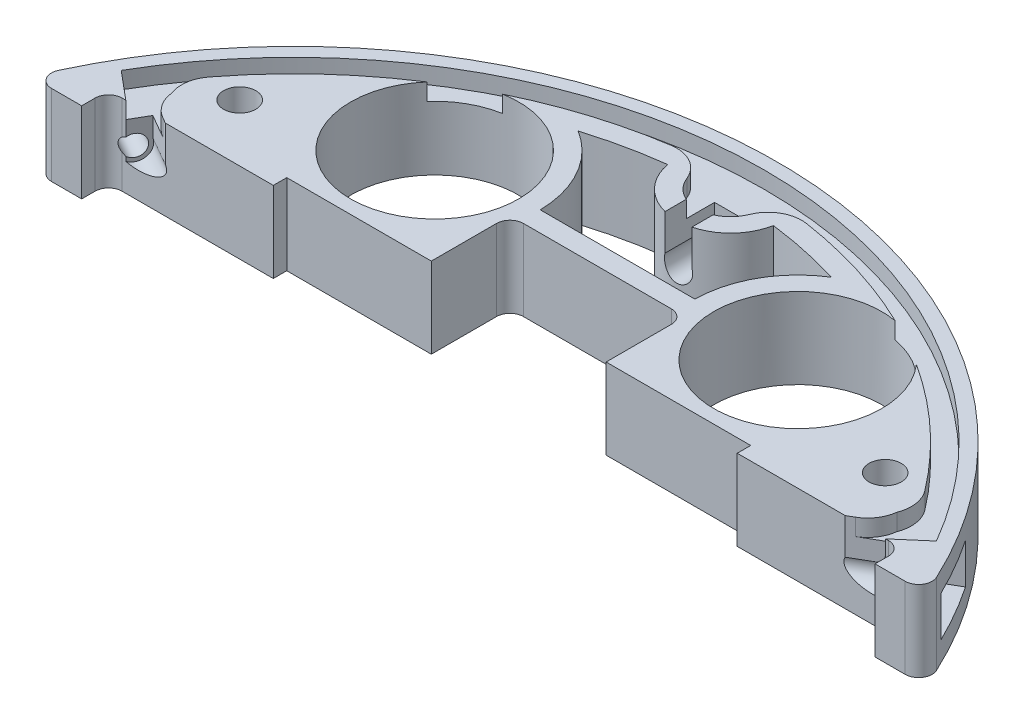
SolidWorks part; units mm, degrees
material "ABS"
ref_plane "Front Plane" through (0, 0, 0) normal (0, 0, 1) x (1, 0, 0)
ref_plane "Top Plane" through (0, 0, 0) normal (0, 1, 0) x (1, 0, 0)
ref_plane "Right Plane" through (0, 0, 0) normal (1, 0, 0) x (0, 0, -1)
sketch "Sketch1" plane through (0, 0, 0) normal (0, 1, 0) x (1, 0, 0)
  line L0 (0, -85) -> (-32.2211, -64.3879) construction
  line L1 (0, -85) -> (0, 0) construction
  arc A0 (36.2245, -62.2237) -> (-36.2245, -62.2237) centre (0, 0) ccw
  arc A1 (29.8119, -61.0352) -> (-29.8119, -61.0352) centre (0, -85) ccw
  arc A2 (36.2245, -62.2237) -> (29.8119, -61.0352) centre (33.7089, -57.9026) cw
  arc A3 (-29.8119, -61.0352) -> (-36.2245, -62.2237) centre (-33.7089, -57.9026) cw
  dimension "D1" = 144
  dimension "D2" = 76.5
  dimension "D4" = 5
  dimension "D3" = 85
extrude "Boss-Extrude1" add sketch "Sketch1" along normal mid plane 12
sketch "solenoid placement" plane through (0, 6, 0) normal (0, 1, 0) x (1, 0, 0)
  line L0 (0, 0) -> (0, -36) construction
  line L5 (-19, -36) -> (19, -36)
  line L7 (19, -36) -> (19, 28)
  line L9 (19, 28) -> (-19, 28)
  line L11 (-19, 28) -> (-19, -36)
  circle A1 centre (0, 0) radius 72 construction
  arc A2 (36.2245, -62.2237) -> (-36.2245, -62.2237) centre (0, 0) ccw construction
  dimension "D1" = 36
  dimension "D2" = 64
  dimension "D3" = 38
extrude "Cut-Extrude1" cut sketch "solenoid placement" against normal through all
sketch "Sketch4" plane through (0, 6, 0) normal (0, 1, 0) x (1, 0, 0)
  line L1 (-13, 28) -> (13, 28)
  line L2 (-13, 28) -> (-13, 43.2)
  line L4 (13, 28) -> (13, 43.2)
  line L5 (11, 45.2) -> (-11, 45.2)
  line L6 (19, 28) -> (-19, 28) construction
  arc A0 (11, 45.2) -> (13, 43.2) centre (11, 43.2) cw
  arc A1 (-11, 45.2) -> (-13, 43.2) centre (-11, 43.2) ccw
  point P6 (0, 28)
  dimension "D1" = 2
  dimension "D2" = 26
  dimension "D3" = 17.2
extrude "Cut-Extrude4" cut sketch "Sketch4" against normal through all
sketch "Sketch5" plane through (0, 6, 0) normal (0, 1, 0) x (1, 0, 0)
  line L0 (0, 0) -> (0, 72) construction
  arc A0 (36.2245, -62.2237) -> (-36.2245, -62.2237) centre (0, 0) ccw construction
  circle A1 centre (27, 48) radius 12.5
  circle A3 centre (-27, 48) radius 12.5
  dimension "D3" = 25
  dimension "D1" = 27
  dimension "D2" = 48
extrude "Cut-Extrude5" cut sketch "Sketch5" against normal through all
sketch "Sketch6" plane through (0, 6, 0) normal (0, 1, 0) x (1, 0, 0)
  line L0 (0, 0) -> (0, 72) construction
  arc A0 (36.2245, -62.2237) -> (-36.2245, -62.2237) centre (0, 0) ccw construction
  circle A1 centre (48, 40) radius 2.4
  circle A6 centre (-48, 40) radius 2.4
  dimension "D3" = 4.8
  dimension "D1" = 48
  dimension "D2" = 40
extrude "Cut-Extrude6" cut sketch "Sketch6" against normal through all
sketch "Sketch3" plane through (0, 6, 0) normal (0, 1, 0) x (1, 0, 0)
  line L1 (-72, -31.5) -> (72, -31.5) construction
  line L2 (-72, -31.5) -> (-72, 27.5)
  line L3 (-59, 31.5) -> (0, 31.5)
  line L4 (72, -31.5) -> (72, 27.5)
  line L5 (0, -31.5) -> (0, 31.5) construction
  line L6 (72, 27.5) -> (59, 27.5)
  line L9 (0, 31.5) -> (59, 31.5)
  line L10 (-72, -31.5) -> (-72, -101.6464)
  line L11 (72, -31.5) -> (72, -101.6464)
  line L12 (72, -101.6464) -> (-72, -101.6464)
  line L13 (59, 27.5) -> (59, 31.5)
  line L14 (-59, 27.5) -> (-59, 31.5)
  line L15 (-72, 27.5) -> (-59, 27.5)
  arc A0 (36.2245, -62.2237) -> (-36.2245, -62.2237) centre (0, 0) ccw construction
  point P0 (0, 0)
  dimension "D2" = 13
  dimension "D1" = 63
  dimension "D3" = 4
extrude "Cut-Extrude3" cut sketch "Sketch3" against normal through all
sketch "Sketch7" plane through (0, 0, 0) normal (0, 1, 0) x (1, 0, 0)
  line L0 (0, 0) -> (62.3538, 36) construction
  line L1 (0, 0) -> (-62.3538, 36) construction
  line L2 (0, 0) -> (0, 72) construction
  arc A0 (0, 72) -> (62.3538, 36) centre (0, 0) cw construction
  arc A1 (0, 72) -> (-62.3538, 36) centre (0, 0) ccw construction
  arc A2 (66.5413, 27.5) -> (-66.5413, 27.5) centre (0, 0) ccw construction
  dimension "D1" = 120
fillet "Fillet1" radius 2 4 edges at (-66.5413, 0, -27.5) (-59, 0, -31.5) (59, 0, -31.5) (66.5413, 0, -27.5)
sketch "Sketch8" plane through (0, 0, 0) normal (0, 1, 0) x (1, 0, 0)
  line L0 (5, 71.8262) -> (5, 68.8262)
  line L1 (0, 0) -> (64.7033, 31.583) construction
  line L2 (64.7033, 31.583) -> (59.7033, 40.2432) construction
  line L3 (64.7033, 31.583) -> (62.1052, 30.083)
  line L4 (62.1052, 30.083) -> (57.1052, 38.7432)
  line L5 (59.7033, 40.2432) -> (57.1052, 38.7432)
  line L6 (0, 0) -> (59.7033, 40.2432) construction
  line L7 (5, 68.8262) -> (-5, 68.8262)
  line L8 (-5, 71.8262) -> (-5, 68.8262)
  line L9 (5, 71.8262) -> (-5, 71.8262) construction
  line L10 (-59.7033, 40.2432) -> (-57.1052, 38.7432)
  line L11 (-57.1052, 38.7432) -> (-62.1052, 30.083)
  line L12 (-64.7033, 31.583) -> (-62.1052, 30.083)
  line L13 (-59.7033, 40.2432) -> (-64.7033, 31.583) construction
  arc A0 (59.7033, 40.2432) -> (64.7033, 31.583) centre (0, 0) cw
  arc A2 (-5, 71.8262) -> (5, 71.8262) centre (0, 0) cw
  arc A3 (-64.7033, 31.583) -> (-59.7033, 40.2432) centre (0, 0) cw
  point P4 (62.3538, 36)
  point P10 (-62.3538, 36)
  point P18 (0, 0)
  dimension "D1" = 10
  dimension "D2" = 3
extrude "Cut-Extrude7" cut sketch "Sketch8" against normal mid plane 6
sketch "Sketch10" plane through (0, 6, 0) normal (0, 1, 0) x (1, 0, 0)
  line L0 (0, 0) -> (0, 65) construction
  circle A0 centre (0, 65) radius 5
  dimension "D2" = 10
  dimension "D1" = 65
extrude "Cut-Extrude9" cut sketch "Sketch10" against normal blind 2.5
sketch "Sketch11" plane through (0, 6, 0) normal (0, 1, 0) x (1, 0, 0)
  line L1 (34.5, -33.5) -> (-34.5, -33.5)
  line L2 (34.5, -33.5) -> (34.5, 33.5)
  line L3 (34.5, 33.5) -> (-34.5, 33.5)
  line L4 (-34.5, -33.5) -> (-34.5, 33.5)
  line L5 (34.5, -33.5) -> (-34.5, 33.5) construction
  line L6 (34.5, 33.5) -> (-34.5, -33.5) construction
  point P0 (0, 0)
  dimension "D1" = 67
  dimension "D2" = 69
extrude "Cut-Extrude10" cut sketch "Sketch11" against normal through all
sketch "Sketch13" plane through (-59.6052, 0, -34.4131) normal (-0.866, 0, -0.5) x (-0.5, 0, 0.866)
  circle A0 centre (0, 0) radius 1.55
  dimension "D1" = 3.1
extrude "Cut-Extrude11" cut sketch "Sketch13" against normal blind 4.2
sketch "Sketch14" plane through (-55.9679, 0, -32.3131) normal (-0.866, 0, -0.5) x (-0.5, 0, 0.866)
  circle A0 centre (0, 0) radius 2.1
  dimension "D1" = 4.2
extrude "Cut-Extrude12" cut sketch "Sketch14" against normal blind 9
sketch "Sketch15" plane through (-55.9679, 0, -32.3131) normal (0.866, 0, 0.5) x (0.5, 0, -0.866)
  line L1 (-2, 0) -> (2, 0)
  line L2 (-2, 0) -> (-2, 10.8827)
  line L3 (-2, 10.8827) -> (2, 10.8827)
  line L4 (2, 0) -> (2, 10.8827)
  point P0 (0, 0)
  dimension "D1" = 4
extrude "Cut-Extrude13" cut sketch "Sketch15" along normal blind 9
pattern_circular "CirPattern1" count 3 over 120 about axis through (0, 6, 0) along (0, -1, 0) of "Cut-Extrude11", "Cut-Extrude12", "Cut-Extrude13"
sketch "Sketch16" plane through (0, 6, 0) normal (0, 1, 0) x (1, 0, 0)
  line L0 (0, 0) -> (-62.3538, 36) construction
  line L1 (0, 0) -> (62.3538, 36) construction
  line L2 (-56.4374, 31.5) -> (-54.9679, 34.0451) construction
  line L4 (-56.4374, 31.5) -> (-60.6218, 35)
  line L5 (3.5, 65) -> (-3.5, 65)
  line L6 (3.5, 65) -> (3.5, 66.9085)
  line L7 (-53.9374, 35.8301) -> (-55.6706, 37.2799)
  line L8 (-3.5, 65) -> (-3.5, 66.9085)
  line L9 (56.4775, 31.4305) -> (60.6218, 35)
  line L10 (53.9775, 35.7607) -> (55.6964, 37.2412)
  line L12 (54.9679, 34.0451) -> (56.4374, 31.5) construction
  line L13 (-53.9374, 35.8301) -> (-56.4374, 31.5)
  line L14 (53.9775, 35.7607) -> (56.4775, 31.4305)
  arc A0 (60.6218, 35) -> (-60.6218, 35) centre (0, 0) ccw
  arc A1 (55.6964, 37.2412) -> (3.5, 66.9085) centre (0, 0) ccw
  arc A2 (2, 60.4174) -> (-2, 60.4174) centre (0, 65) ccw construction
  arc A3 (-3.5, 66.9085) -> (-55.6706, 37.2799) centre (0, 0) ccw
  arc A4 (59, 29.5) -> (57, 31.5) centre (57, 29.5) ccw construction
  point P15 (0, 65)
  dimension "D1" = 3
  dimension "D2" = 140
  dimension "D3" = 7
  dimension "D4" = 5
  dimension "D5" = 5
extrude "Cut-Extrude14" cut sketch "Sketch16" against normal blind 2.5
fillet "Fillet2" radius 5 6 edges at (55.6964, 4.75, -37.2412) (-55.6706, 4.75, -37.2799) (54.9679, 4.75, -34.0451) (-54.9679, 4.75, -34.0451) (4.6497, 4.75, -66.8385) (-4.6497, 4.75, -66.8385)
sketch "Sketch17" plane through (0, 6, 0) normal (0, 1, 0) x (1, 0, 0)
  line L2 (11, 48.2) -> (-11, 48.2)
  line L3 (11.5013, 48.2) -> (-11.5013, 48.2)
  arc A2 (-38.6301, 58.2465) -> (-29.7173, 63.26) centre (-27, 48) ccw
  arc A3 (-11.5013, 48.2) -> (-18.8249, 61.1688) centre (-27, 48) ccw
  arc A5 (29.7173, 63.26) -> (38.6301, 58.2465) centre (27, 48) ccw
  arc A6 (18.8249, 61.1688) -> (11.5013, 48.2) centre (27, 48) ccw
  arc A8 (3.2, 57.6679) -> (7.4323, 62.04) centre (0, 65) ccw
  arc A9 (-7.861, 63.5154) -> (7.861, 63.5154) centre (0, 65) ccw
  arc A11 (-9.59, 63.2774) -> (-27.8843, 57.6061) centre (0, 0) ccw
  arc A12 (-7.861, 63.5154) -> (-18.8249, 61.1688) centre (0, 0) ccw
  arc A14 (27.8843, 57.6061) -> (9.59, 63.2774) centre (0, 0) ccw
  arc A15 (18.8249, 61.1688) -> (7.861, 63.5154) centre (0, 0) ccw
  dimension "D1" = 3
  dimension "D2" = 3
  dimension "D3" = 3
  dimension "D4" = 3
  dimension "D5" = 3
  dimension "D6" = 3
extrude "Cut-Extrude15" cut sketch "Sketch17" against normal through all
equation "\"smallPulleyTeeth\"= 30"
equation "\"largePulleyTeeth\"= 30"
equation "\"eighthThick\"= 3.0mm"
equation "\"sixteenthThick\"= 1.7mm"
equation "\"quarterThick\"=6.0mm"
equation "\"OD\"= 145mm"
equation "\"puckAngle\"= 60.5deg"
equation "\"puckDiam\"= 76.5mm"
equation "\"D2@Sketch1\"=\"puckDiam\""
equation "\"D1@Boss-Extrude1\"=\"eighthThick\"*4"
equation "\"axlePress\"= 5.9mm"
equation "\"press\"= 0.2mm"
equation "\"wheelClear\"= 0.3mm"
equation "\"10-32clear\"= 4.8mm"
equation "\"6-32clear\"= 3.3mm"
equation "\"8-32clear\"= 4.0mm"
equation "\"wheelHeight\"= 22mm"
equation "\"wheelWell\"= 65mm"
equation "\"puckDist\"= 85mm"
equation "\"scoopFillet\"= 5mm"
equation "\"4-40clear\"= 3.0mm"
equation "\"D3@Sketch1\"=\"puckDist\""
equation "\"D4@Sketch1\"=\"scoopFillet\""
equation "\"D3@Sketch6\"=\"10-32clear\""
equation "\"D2@Sketch8\"=\"eighthThick\""
equation "\"10-32tap\"= 4.45mm"
equation "\"ledSmall\"= 3.1mm"
equation "\"ledLarge\"= 4.2mm"
equation "\"ledLength\"= 4.2mm"
equation "\"D1@Sketch13\"=\"ledSmall\""
equation "\"D1@Cut-Extrude11\"=\"ledLength\""
equation "\"D1@Sketch14\"=\"ledLarge\""
